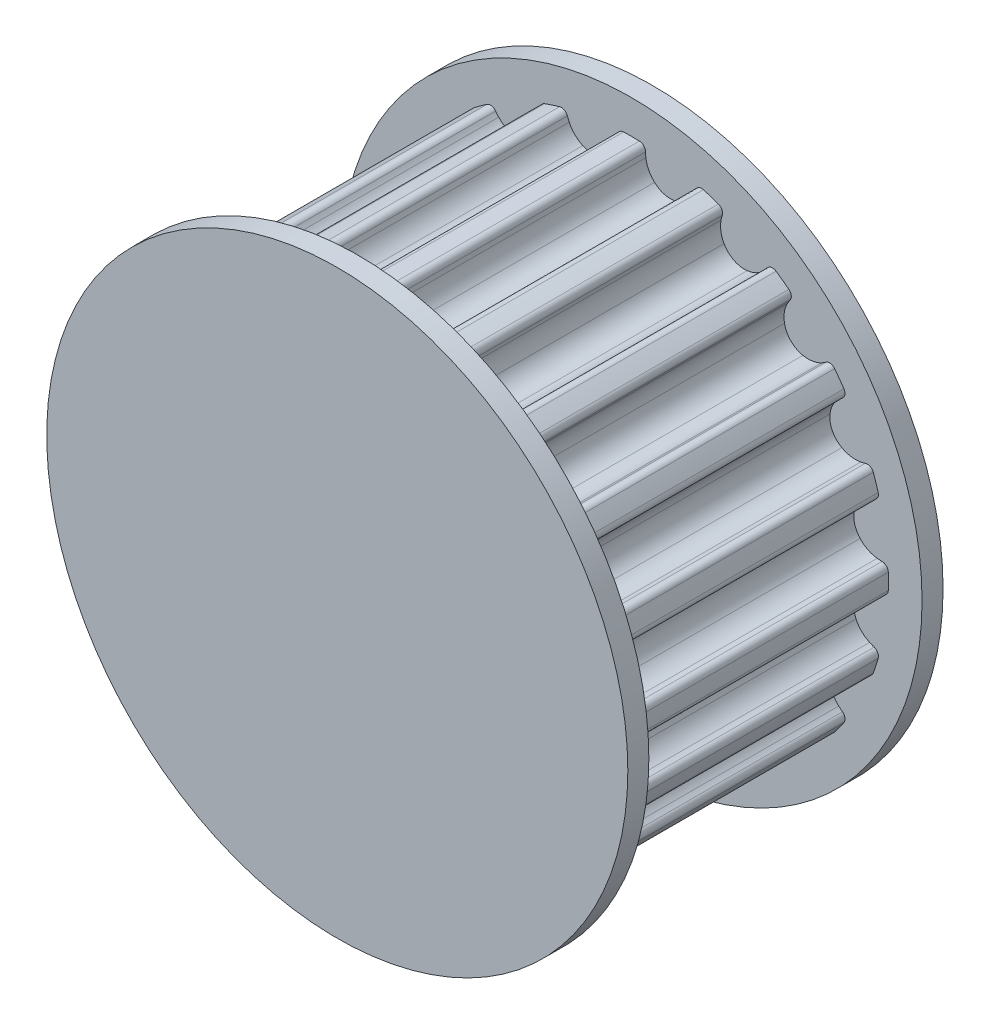
SolidWorks part; units mm, degrees
ref_plane "Front Plane" through (0, 0, 0) normal (0, 0, 1) x (1, 0, 0)
ref_plane "Top Plane" through (0, 0, 0) normal (0, 1, 0) x (1, 0, 0)
ref_plane "Right Plane" through (0, 0, 0) normal (1, 0, 0) x (0, 0, -1)
sketch "Sketch1" plane through (0, 0, 0) normal (0, 0, 1) x (1, 0, 0)
  line L0 (0, 0) -> (0, 6.3662) construction
  line L1 (0, 0) -> (0.9959, 6.2878) construction
  line L2 (0, 0) -> (1.3887, 6.2129) construction
  circle A0 centre (0, 0) radius 6.3662 construction
  circle A1 centre (0, 0) radius 5.3622 construction
  circle A2 centre (0, 0) radius 6.1122 construction
  arc A3 (0.8388, 5.2962) -> (0.5472, 5.4384) centre (0.9257, 5.8443) cw
  arc A4 (0.3406, 5.8443) -> (0.3333, 5.9601) centre (1.3333, 5.965) cw
  circle A5 centre (0, 0) radius 5.9622 construction
  arc A6 (-0.188, 6.1093) -> (0.188, 6.1093) centre (0, 0) cw
  arc A7 (0.188, 6.1093) -> (0.3333, 5.9601) centre (0.1833, 5.9594) cw
  arc A8 (0.3406, 5.8443) -> (0.5472, 5.4384) centre (1.0004, 5.9245) ccw
  arc A9 (-0.8388, 5.2962) -> (-0.5472, 5.4384) centre (-0.9257, 5.8443) ccw
  arc A10 (-0.3406, 5.8443) -> (-0.5472, 5.4384) centre (-1.0004, 5.9245) cw
  arc A11 (-0.3406, 5.8443) -> (-0.3333, 5.9601) centre (-1.3333, 5.965) ccw
  arc A12 (-0.188, 6.1093) -> (-0.3333, 5.9601) centre (-0.1833, 5.9594) ccw
  arc A13 (-0.8388, 5.2962) -> (0.8388, 5.2962) centre (0, 0) cw
  dimension "D1" = 12.7324
  dimension "D6" = 0.555
  dimension "D7" = 1
  dimension "D9" = 0.15
  dimension "D2" = 9
  dimension "D3" = 3.6
  dimension "D4" = 1.004
  dimension "D5" = 0.75
  dimension "D8" = 0.15
extrude "Boss-Extrude1" add sketch "Sketch1" along normal blind 6.5
ref_axis "Axis1" through (0, 0, -0.375) along (0, 0, 1)
pattern_circular "CirPattern1" count 20 over 360 about axis through (0, 0, -0.375) along (0, 0, 1) of bodies 107
sketch "Sketch2" plane through (0, 0, 0) normal (0, 0, -1) x (-1, 0, 0)
  circle A0 centre (0, 0) radius 5.3622
  arc A1 (0.8388, 5.2962) -> (-0.8388, 5.2962) centre (0, 0) ccw construction
extrude "Boss-Extrude2" add sketch "Sketch2" against normal up to surface (6.5 mm away)
sketch "Schizzo1" plane through (0, 0, 6.5) normal (0, 0, 1) x (1, 0, 0)
  circle A0 centre (0, 0) radius 6.9122
  arc A1 (-6.1093, 0.188) -> (-6.1093, -0.188) centre (0, 0) ccw construction
  dimension "D1" = 0.8
extrude "Estrusione-Estrusione1" add sketch "Schizzo1" along normal blind 0.5
ref_plane "Piano1" through (0, 0, 3.25) normal (0, 0, -1) x (-1, 0, 0)
mirror "Specchia1" about plane through (0, 0, 3.25) normal (0, 0, -1) of "Estrusione-Estrusione1"
equation "\"NumTeeth\" = 20'The number of teeth that the pulley has"
equation "\"ToothPitch\"= 2.00mm'Distance between 2 teeth"
equation "\"PulleyDia\"= \"NumTeeth\" * \"ToothPitch\" / PI"
equation "\"ToothAng\"= ( 360deg / \"NumTeeth\" ) * 1deg"
equation "\"TransOffsetAngle\"= \"ToothAng\" * .2deg"
equation "\"ShoulderRad\"= 0.15mm"
equation "\"RootRad\"= 0.555mm"
equation "\"TransRad\"= 1mm"
equation "\"ToothHeight\"= 0.75mm"
equation "\"PLD\"= 0.254mm"
equation "\"D1@CirPattern1\"=\"NumTeeth\""
equation "\"D1@Sketch1\"=\"PulleyDia\""
equation "\"D7@Sketch1\"=\"TransRad\""
equation "\"D9@Sketch1\"=\"ShoulderRad\""
equation "\"D6@Sketch1\"=\"RootRad\""
equation "\"D3@Sketch1\"=\"TransOffsetAngle\""
equation "\"D5@Sketch1\"=\"ToothHeight\""
equation "\"D2@Sketch1\"=\"ToothAng\"/2"
equation "\"D4@Sketch1\"=\"PLD\"+\"ToothHeight\""
equation "\"D8@Sketch1\"=\"ShoulderRad\""
equation "\"altezza\"= 6.5mm"
equation "\"D1@Boss-Extrude1\"=\"altezza\""
